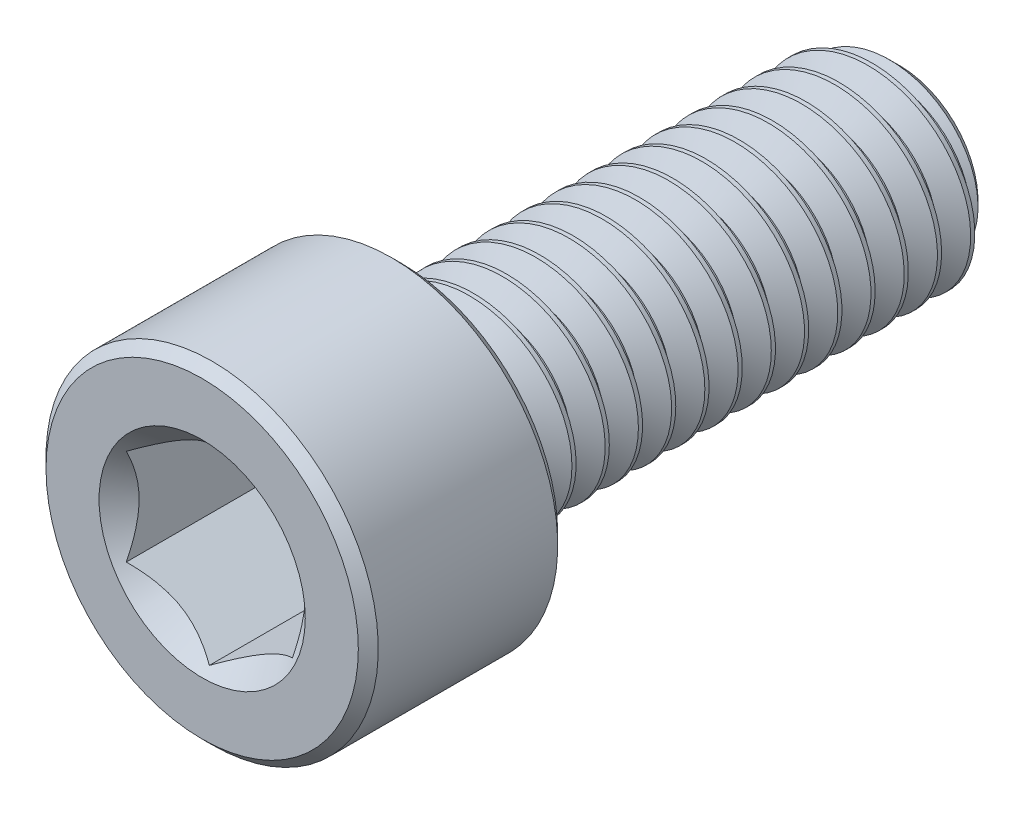
SolidWorks part; units mm, degrees
ref_plane "Front Plane" through (0, 0, 0) normal (0, 0, 1) x (1, 0, 0)
ref_plane "Top Plane" through (0, 0, 0) normal (0, 1, 0) x (1, 0, 0)
ref_plane "Right Plane" through (0, 0, 0) normal (1, 0, 0) x (0, 0, -1)
sketch "Sketch1" plane through (0, 0, 0) normal (1, 0, 0) x (0, 0, -1)
  line L0 (-10.5, 0) -> (10.5, 0) construction
  line L1 (10.5, 0) -> (10.5, 2.3505) construction
  line L2 (10.5, 2.3505) -> (9.8505, 3) construction
  line L3 (9.8505, 3) -> (9.75, 3) construction
  line L4 (9.75, 3) -> (-4.5, 3) construction
  line L5 (-4.5, 3) -> (-4.5, 5) construction
  line L6 (-4.5, 5) -> (-10.5, 5) construction
  line L7 (-10.5, 5) -> (-10.5, 0) construction
  line L8 (10.5, 2.3505) -> (10.5, 3) construction
  line L9 (10.4375, 3.1083) -> (10.9375, 2.2422) construction
  line L10 (10.9375, 2.2422) -> (11.4375, 3.1083) construction
  line L11 (11.4375, 3.1083) -> (10.4375, 3.1083) construction
  line L12 (10.9375, 3.1083) -> (10.9375, 3) construction
  line L13 (10.9375, 2.2422) -> (10.9375, 2.3505) construction
  line L14 (10.875, 2.3505) -> (11, 2.3505) construction
  line L15 (10.5, 3) -> (11.375, 3) construction
  line L16 (10.4687, 3.0541) -> (11.4063, 3.0541) construction
  line L17 (10.5, 0) -> (10.5, -3) construction
  line L18 (-4.8, 5) -> (-4.5, 4.7) construction
  line L19 (-10.2, 5) -> (-10.5, 4.7) construction
  line L20 (-4.5, 3) -> (-4.5, 0) construction
  line L21 (-4.5, 1.5) -> (0.5, 1.5) construction
  line L22 (0.5, 1.5) -> (5.5, 1.5) construction
  line L23 (5.5, 1.5) -> (10.5, 1.5) construction
  line L24 (0.5, 1.5) -> (0.5, 3) construction
  line L25 (0.5, 3) -> (0.5, 5) construction
  line L26 (5.5, 1.5) -> (5.5, 5) construction
  point P0 (-10.5, 2.5)
  point P3 (8, 3)
  point P4 (0, 0)
  point P18 (5.5, 3)
  point P22 (10.9375, 2.3505)
  point P24 (9.75, 3)
  point P25 (10.9375, 3)
  point P28 (10.9375, 3.0541)
  point P29 (8, -3)
  point P30 (0.5, 3)
  point P31 (-7.5, 5)
  point P37 (-5.55, 5)
  point P38 (-10.05, 5)
  point P45 (0.5, 1.5)
  point P46 (5.5, 1.5)
  dimension "D2" = 0.125
  dimension "D7" = 0.3
  dimension "D8" = 0.3
  dimension "D9" = 0.3
  dimension "D10" = 0.15
  dimension "D11" = 0.75
  dimension "Drive Size" = 5
  dimension "Head Diameter" = 10
  dimension "Head Height" = 6
  dimension "Thread Pitch" = 1
  dimension "Thread Size" = 6
  dimension "Length" = 15
  dimension "D12" = 0.75
  dimension "D4" = 2.5
  dimension "D3" = 45
sketch "Sketch2" plane through (0, 0, 0) normal (1, 0, 0) x (0, 0, -1)
  line L0 (-10.5, 0) -> (-10.5, 4.7)
  line L1 (-10.2, 5) -> (-4.8, 5)
  line L2 (-4.5, 4.7) -> (-4.5, 3.3)
  line L4 (9.8505, 3) -> (10.5, 2.3505)
  line L5 (10.5, 2.3505) -> (10.5, 0)
  line L6 (-4.5, 5) -> (-10.5, 5) construction
  line L7 (10.5, 0) -> (-10.5, 0)
  line L8 (-10.2, 5) -> (-10.5, 4.7) construction
  line L10 (-10.2, 5) -> (-10.5, 4.7)
  line L14 (-4.8, 5) -> (-4.5, 4.7) construction
  line L16 (-4.8, 5) -> (-4.5, 4.7)
  line L17 (-4.5, 3) -> (-4.5, 5) construction
  line L19 (-4.2, 3) -> (9.8505, 3)
  line L20 (9.75, 3) -> (-4.5, 3) construction
  arc A1 (-4.5, 3.3) -> (-4.2, 3) centre (-4.2, 3.3) ccw
  dimension "D3" = 0.3
revolve "Revolve1" add sketch "Sketch2" angle 360 about L7
sketch "Sketch3" plane through (0, 0, 10.5) normal (0, 0, 1) x (1, 0, 0)
  line L1 (2.5, -1.4434) -> (2.5, 1.4434)
  line L2 (2.5, 1.4434) -> (0, 2.8868)
  line L3 (0, 2.8868) -> (-2.5, 1.4434)
  line L4 (-2.5, 1.4434) -> (-2.5, -1.4434)
  line L5 (-2.5, -1.4434) -> (0, -2.8868)
  line L6 (0, -2.8868) -> (2.5, -1.4434)
  circle A0 centre (0, 0) radius 2.5 construction
  circle A1 centre (0, 0) radius 5 construction
  circle A2 centre (0, 0) radius 5 construction
  circle A3 centre (0, 0) radius 2.8868 construction
  point P13 (0, 0)
  dimension "D1" = 5.7735
extrude "Cut-Extrude1" cut sketch "Sketch3" against normal offset from surface (5 mm away) 1 up to face at (0, 4.7, 4.5)
sketch "Sketch4" plane through (0, 0, 10.5) normal (0, 0, 1) x (1, 0, 0)
  circle A0 centre (0, 0) radius 3.1033
  dimension "D1" = 6.2065
extrude "Cut-Extrude2" cut sketch "Sketch4" against normal up to vertex (3 mm away) draft 45 up to point (0, 5, 7.5)
sketch "Sketch11" plane through (0, 0, 0) normal (1, 0, 0) x (0, 0, -1)
  line L0 (-10.5, 0) -> (10.5, 0) construction
  line L1 (-10.5, 0) -> (10.5, 0) construction
  line L2 (-1.6875, 0) -> (-1.6875, 3) construction
  line L3 (9.75, 3) -> (-4.5, 3) construction
  line L4 (7.6875, 0) -> (7.6875, 3) construction
  line L6 (10.5, 2.3505) -> (10.5, 3) construction
  point P2 (-1.6875, 0)
  point P3 (7.6875, 0)
  dimension "D1" = 2.8125
  dimension "D2" = 2.8125
sketch "Sketch6" plane through (0, 0, -10.5) normal (0, 0, -1) x (-1, 0, 0)
  circle A0 centre (0, 0) radius 3
curve "Helix/Spiral1" pitch 1 height 16 radius 3 centre (0, 0, -10.5) axis (0, 0, 1) start towards (0, 1, 0)
sketch "Sketch10" plane through (0, 0, 0) normal (1, 0, 0) x (0, 0, -1)
  line L0 (-4.2, -5) -> (-4.2, 5)
  line L5 (-10.5, 0) -> (10.5, 0) construction
  line L6 (-4.2, 3) -> (-4.2, -3) construction
  point P3 (-4.2, 0)
split "Split1" trim tools "Sketch10" bodies to split 106 resulting bodies 114 115
sketch "Sketch7" plane through (0, 0, 0) normal (1, 0, 0) x (0, 0, -1)
  line L0 (10.4687, 3.0541) -> (11.4063, 3.0541)
  line L1 (11.4063, 3.0541) -> (11, 2.3505)
  line L2 (11, 2.3505) -> (10.875, 2.3505)
  line L3 (10.875, 2.3505) -> (10.4687, 3.0541)
sweep "Cut-Sweep1" cut profiles "Sketch7" path "Helix/Spiral1" align with end faces yes
sketch "Sketch8" plane through (0, 0, 0) normal (1, 0, 0) x (0, 0, -1)
  line L0 (-4.5, 0) -> (-4.5, 3)
  line L1 (-4.2, -3) -> (-4.2, 3) construction
  line L2 (-4.5, 3) -> (-4.2, 3)
  line L4 (-4.2, 3) -> (-2.4679, 0)
  line L5 (-2.4679, 0) -> (-4.5, 0)
  line L6 (9.75, 3) -> (-4.5, 3) construction
  line L7 (-10.5, 0) -> (10.5, 0) construction
  dimension "D1" = 60
revolve "Revolve2" add sketch "Sketch8" angle 360 about L5
equation "\"D2@Sketch1\" = \"Thread Pitch@Sketch1\" / 8"
equation "\"D4@Helix/Spiral1\" = \"Thread Pitch@Sketch1\""
equation "\"D7@Sketch1\" = \"Head Height@Sketch1\" * .05"
equation "\"D8@Sketch1\"=\"D7@Sketch1\""
equation "\"D9@Sketch1\"=\"D7@Sketch1\""
equation "\"D10@Sketch1\"=\"D7@Sketch1\"/2"
equation "\"D11@Sketch1\"=\"D10@Sketch1\"*5"
equation "\"D4@Sketch1\"=\"Thread Pitch@Sketch1\"*2.5"
equation "\"D12@Sketch1\"=\"Thread Pitch@Sketch1\"*.75"
equation "\"D3@Helix/Spiral1\"=\"Length@Sketch1\"+\"Thread Pitch@Sketch1\""
equation "\"D3@Sketch2\"=\"Thread Size@Sketch1\"*0.05"
equation "\"D1@Sketch11\"=\"Length@Sketch1\"*0.1875"
equation "\"D2@Sketch11\"=\"D1@Sketch11\""
equation "\"D1@Sketch4\"=\"D1@Sketch3\"*1.075"
